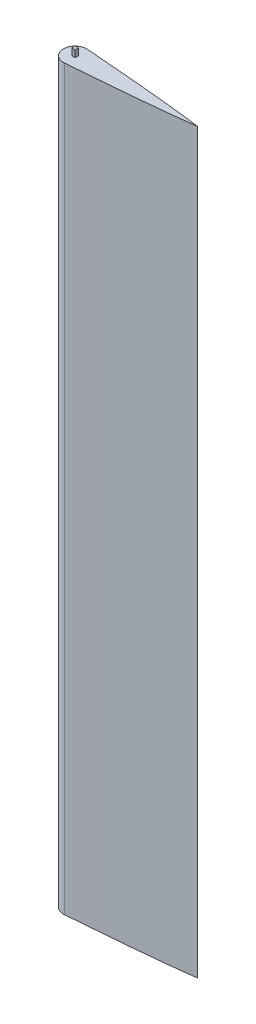
SolidWorks part; units mm, degrees
ref_plane "Front Plane" through (0, 0, 0) normal (0, 0, 1) x (1, 0, 0)
ref_plane "Top Plane" through (0, 0, 0) normal (0, 1, 0) x (1, 0, 0)
ref_plane "Right Plane" through (0, 0, 0) normal (1, 0, 0) x (0, 0, -1)
curve "Кривая1"
  spline degree 3 poles (1000, 0, 0) (1000.0041, 0, -0.0513) (1000.0182, 0, -0.2257) (1000.1688, 0, -0.5403) (1000.4745, 0, -0.9506) (1001.0036, 0, -1.4445) (1001.8807, 0, -2.0291) (1003.2737, 0, -2.6418) (1005.1875, 0, -3.2144) (1007.4906, 0, -3.7219) (1009.9978, 0, -4.1606) (1012.5898, 0, -4.5274) (1015.2222, 0, -4.8264) (1017.8799, 0, -5.0656) (1020.5573, 0, -5.2577) (1023.2491, 0, -5.4066) (1025.9511, 0, -5.5212) (1028.6617, 0, -5.6021) (1031.3775, 0, -5.6554) (1034.0978, 0, -5.6836) (1036.8218, 0, -5.6855) (1039.5499, 0, -5.6668) (1042.2813, 0, -5.629) (1045.0148, 0, -5.5734) (1047.7503, 0, -5.5016) (1050.4877, 0, -5.4147) (1053.2265, 0, -5.3143) (1055.9663, 0, -5.2015) (1058.7068, 0, -5.0768) (1061.4478, 0, -4.941) (1064.1895, 0, -4.7947) (1066.9318, 0, -4.6386) (1069.6745, 0, -4.4734) (1072.4174, 0, -4.2996) (1075.1604, 0, -4.1176) (1077.9035, 0, -3.9277) (1080.6469, 0, -3.7302) (1083.3903, 0, -3.5256) (1086.1334, 0, -3.3144) (1088.876, 0, -3.0964) (1091.618, 0, -2.8714) (1094.3597, 0, -2.6396) (1097.1011, 0, -2.4012) (1099.8418, 0, -2.1563) (1102.5808, 0, -1.9046) (1105.3171, 0, -1.6455) (1108.0495, 0, -1.3772) (1110.7765, 0, -1.0976) (1113.4879, 0, -0.8078) (1116.1278, 0, -0.5051) (1118.2949, 0, -0.236) (1119.5657, 0, -0.0601) (1120, 0, 0) knots 0 0 0 0 0.001266 0.004299 0.008398 0.013889 0.022051 0.034303 0.051281 0.071284 0.092472 0.114086 0.135878 0.157846 0.179936 0.202121 0.224378 0.246676 0.269043 0.291412 0.313814 0.336267 0.358739 0.381229 0.40374 0.426271 0.448818 0.471377 0.493944 0.51652 0.539106 0.561702 0.584306 0.606915 0.629529 0.652149 0.674775 0.697407 0.720041 0.742673 0.765305 0.787939 0.810576 0.833214 0.855845 0.878458 0.901044 0.923602 0.94611 0.968341 0.989179 1 1 1 1
curve "Кривая2"
  spline degree 3 poles (1120, 0, 0) (1119.5657, 0, 0.0601) (1118.2949, 0, 0.236) (1116.1278, 0, 0.5051) (1113.4879, 0, 0.8078) (1110.7765, 0, 1.0976) (1108.0495, 0, 1.3772) (1105.3171, 0, 1.6455) (1102.5808, 0, 1.9046) (1099.8418, 0, 2.1563) (1097.1011, 0, 2.4012) (1094.3597, 0, 2.6396) (1091.618, 0, 2.8714) (1088.876, 0, 3.0964) (1086.1334, 0, 3.3144) (1083.3903, 0, 3.5256) (1080.6469, 0, 3.7302) (1077.9035, 0, 3.9277) (1075.1604, 0, 4.1176) (1072.4174, 0, 4.2996) (1069.6745, 0, 4.4734) (1066.9318, 0, 4.6386) (1064.1895, 0, 4.7947) (1061.4478, 0, 4.941) (1058.7068, 0, 5.0768) (1055.9663, 0, 5.2015) (1053.2265, 0, 5.3143) (1050.4877, 0, 5.4147) (1047.7503, 0, 5.5016) (1045.0148, 0, 5.5734) (1042.2813, 0, 5.629) (1039.5499, 0, 5.6668) (1036.8218, 0, 5.6855) (1034.0978, 0, 5.6836) (1031.3775, 0, 5.6554) (1028.6617, 0, 5.6021) (1025.9511, 0, 5.5212) (1023.2491, 0, 5.4066) (1020.5573, 0, 5.2577) (1017.8799, 0, 5.0656) (1015.2222, 0, 4.8264) (1012.5898, 0, 4.5274) (1009.9978, 0, 4.1606) (1007.4906, 0, 3.7219) (1005.1875, 0, 3.2144) (1003.2737, 0, 2.6418) (1001.8807, 0, 2.0291) (1001.0036, 0, 1.4445) (1000.4745, 0, 0.9506) (1000.1688, 0, 0.5403) (1000.0182, 0, 0.2257) (1000.0041, 0, 0.0513) (1000, 0, 0) knots 0 0 0 0 0.010821 0.031659 0.05389 0.076398 0.098956 0.121542 0.144155 0.166786 0.189424 0.212061 0.234695 0.257327 0.279959 0.302593 0.325225 0.347851 0.370471 0.393085 0.415694 0.438298 0.460894 0.48348 0.506056 0.528623 0.551182 0.573729 0.59626 0.618771 0.641261 0.663733 0.686186 0.708588 0.730957 0.753324 0.775622 0.797879 0.820064 0.842154 0.864122 0.885914 0.907528 0.928716 0.948719 0.965697 0.977949 0.986111 0.991602 0.995701 0.998734 1 1 1 1
sketch "Эскиз2" plane through (0, 0, 0) normal (0, 1, 0) x (1, 0, 0)
  line L0 (1000, 0) -> (1120, 0) construction
  line L1 (1080, 14.3701) -> (1080, -24.9221) construction
  line L3 (1083.0057, -0.5) -> (1084.0057, -0.5)
  line L4 (1083.0057, -0.5) -> (1083.0057, 0.5)
  line L5 (1083.0057, 0.5) -> (1084.0057, 0.5)
  line L6 (1084.0057, -0.5) -> (1084.0057, 0.5)
  line L7 (1083.0057, -0.5) -> (1084.0057, 0.5) construction
  line L8 (1083.0057, 0.5) -> (1084.0057, -0.5) construction
  arc A0 (1083.7717, 3.4955) -> (1083.7717, -3.4955) centre (1083.5057, 0) ccw
  spline S0 degree 3 poles (1956.2165, -4926.245) (1230.5192, 53.0849) (1176.3623, 6.9741) (1116.1278, -0.5051) (1113.4879, -0.8078) (1110.7765, -1.0976) (1108.0495, -1.3772) (1105.3171, -1.6455) (1102.5808, -1.9046) (1099.8418, -2.1563) (1097.1011, -2.4012) (1094.3597, -2.6396) (1091.618, -2.8714) (1087.9619, -3.1714) (1083.3908, -3.5289) (1078.8184, -3.8643) (1074.2464, -4.1809) (1070.5892, -4.4183) (1066.9318, -4.6386) (1064.1895, -4.7947) (1060.5347, -4.9897) (1056.8803, -5.1639) (1053.2265, -5.3143) (1050.4877, -5.4147) (1046.8394, -5.5305) (1043.1934, -5.6163) (1039.5499, -5.6668) (1036.8218, -5.6855) (1034.0978, -5.6836) (1031.3775, -5.6554) (1028.6617, -5.6021) (1025.9511, -5.5212) (1023.2491, -5.4066) (1020.5573, -5.2577) (1017.8799, -5.0656) (1015.2222, -4.8264) (1012.5898, -4.5274) (1009.9978, -4.1606) (1007.4906, -3.7219) (1005.1875, -3.2144) (1003.2737, -2.6418) (1001.8807, -2.0291) (1001.0036, -1.4445) (1000.4745, -0.9506) (1000.1688, -0.5403) (997.8298, 4.3449) (1049.9935, 20.5033) (-3894.0582, -1012.3547) knots -1.443989 -1.443989 -1.443989 -1.443989 0.010821 0.031659 0.05389 0.076398 0.098956 0.121542 0.144155 0.166786 0.189424 0.212061 0.234695 0.257327 0.302593 0.347851 0.370471 0.415694 0.438298 0.460894 0.48348 0.528623 0.551182 0.573729 0.59626 0.641261 0.663733 0.686186 0.708588 0.730957 0.753324 0.775622 0.797879 0.820064 0.842154 0.864122 0.885914 0.907528 0.928716 0.948719 0.965697 0.977949 0.986111 0.991602 0.995701 0.998734 1.121986 1.121986 1.121986 1.121986 only from (1120, 0) to (1000, 0) construction
  spline S1 degree 3 poles (-3893.3459, 1012.2059) (1049.9886, -20.5018) (997.8299, -4.3447) (1000.1688, 0.5403) (1000.4745, 0.9506) (1001.0036, 1.4445) (1001.8807, 2.0291) (1003.2737, 2.6418) (1005.1875, 3.2144) (1007.4906, 3.7219) (1009.9978, 4.1606) (1012.5898, 4.5274) (1015.2222, 4.8264) (1017.8799, 5.0656) (1020.5573, 5.2577) (1023.2491, 5.4066) (1025.9511, 5.5212) (1028.6617, 5.6021) (1031.3775, 5.6554) (1034.0978, 5.6836) (1036.8218, 5.6855) (1039.5499, 5.6668) (1043.1934, 5.6163) (1046.8394, 5.5305) (1050.4877, 5.4147) (1053.2265, 5.3143) (1056.8803, 5.1639) (1060.5347, 4.9897) (1064.1895, 4.7947) (1066.9318, 4.6386) (1070.5892, 4.4183) (1074.2464, 4.1809) (1078.8184, 3.8643) (1082.4762, 3.596) (1086.1334, 3.3144) (1088.876, 3.0964) (1091.618, 2.8714) (1094.3597, 2.6396) (1097.1011, 2.4012) (1099.8418, 2.1563) (1102.5808, 1.9046) (1105.3171, 1.6455) (1108.0495, 1.3772) (1110.7765, 1.0976) (1113.4879, 0.8078) (1116.1278, 0.5051) (1176.3634, -6.9742) (1230.5211, -53.0865) (1956.254, 4926.5023) knots -0.12198 -0.12198 -0.12198 -0.12198 0.001266 0.004299 0.008398 0.013889 0.022051 0.034303 0.051281 0.071284 0.092472 0.114086 0.135878 0.157846 0.179936 0.202121 0.224378 0.246676 0.269043 0.291412 0.313814 0.336267 0.358739 0.40374 0.426271 0.448818 0.471377 0.51652 0.539106 0.561702 0.584306 0.629529 0.652149 0.697407 0.720041 0.742673 0.765305 0.787939 0.810576 0.833214 0.855845 0.878458 0.901044 0.923602 0.94611 0.968341 0.989179 2.444014 2.444014 2.444014 2.444014 only from (1000, 0) to (1120, 0) construction
  spline S2 degree 3 poles (1120, 0) (1119.5657, -0.0601) (1118.2949, -0.236) (1116.1278, -0.5051) (1113.4879, -0.8078) (1110.7765, -1.0976) (1108.0495, -1.3772) (1105.3171, -1.6455) (1102.5808, -1.9046) (1099.8418, -2.1563) (1097.1011, -2.4012) (1094.3597, -2.6396) (1091.618, -2.8714) (1087.9619, -3.1714) (1083.3908, -3.5289) (1078.8184, -3.8643) (1074.2464, -4.1809) (1070.5892, -4.4183) (1066.9318, -4.6386) (1064.1895, -4.7947) (1060.5347, -4.9897) (1056.8803, -5.1639) (1053.2265, -5.3143) (1050.4877, -5.4147) (1046.8394, -5.5305) (1043.1934, -5.6163) (1039.5499, -5.6668) (1036.8218, -5.6855) (1034.0978, -5.6836) (1031.3775, -5.6554) (1028.6617, -5.6021) (1025.9511, -5.5212) (1023.2491, -5.4066) (1020.5573, -5.2577) (1017.8799, -5.0656) (1015.2222, -4.8264) (1012.5898, -4.5274) (1009.9978, -4.1606) (1007.4906, -3.7219) (1005.1875, -3.2144) (1003.2737, -2.6418) (1001.8807, -2.0291) (1001.0036, -1.4445) (1000.4745, -0.9506) (1000.1688, -0.5403) (1000.0182, -0.2257) (1000.0041, -0.0513) (1000, 0) knots 0 0 0 0 0.010821 0.031659 0.05389 0.076398 0.098956 0.121542 0.144155 0.166786 0.189424 0.212061 0.234695 0.257327 0.302593 0.347851 0.370471 0.415694 0.438298 0.460894 0.48348 0.528623 0.551182 0.573729 0.59626 0.641261 0.663733 0.686186 0.708588 0.730957 0.753324 0.775622 0.797879 0.820064 0.842154 0.864122 0.885914 0.907528 0.928716 0.948719 0.965697 0.977949 0.986111 0.991602 0.995701 0.998734 1 1 1 1
  spline S3 degree 3 poles (1000, 0) (1000.0041, 0.0513) (1000.0182, 0.2257) (1000.1688, 0.5403) (1000.4745, 0.9506) (1001.0036, 1.4445) (1001.8807, 2.0291) (1003.2737, 2.6418) (1005.1875, 3.2144) (1007.4906, 3.7219) (1009.9978, 4.1606) (1012.5898, 4.5274) (1015.2222, 4.8264) (1017.8799, 5.0656) (1020.5573, 5.2577) (1023.2491, 5.4066) (1025.9511, 5.5212) (1028.6617, 5.6021) (1031.3775, 5.6554) (1034.0978, 5.6836) (1036.8218, 5.6855) (1039.5499, 5.6668) (1043.1934, 5.6163) (1046.8394, 5.5305) (1050.4877, 5.4147) (1053.2265, 5.3143) (1056.8803, 5.1639) (1060.5347, 4.9897) (1064.1895, 4.7947) (1066.9318, 4.6386) (1070.5892, 4.4183) (1074.2464, 4.1809) (1078.8184, 3.8643) (1082.4762, 3.596) (1086.1334, 3.3144) (1088.876, 3.0964) (1091.618, 2.8714) (1094.3597, 2.6396) (1097.1011, 2.4012) (1099.8418, 2.1563) (1102.5808, 1.9046) (1105.3171, 1.6455) (1108.0495, 1.3772) (1110.7765, 1.0976) (1113.4879, 0.8078) (1116.1278, 0.5051) (1118.2949, 0.236) (1119.5657, 0.0601) (1120, 0) knots 0 0 0 0 0.001266 0.004299 0.008398 0.013889 0.022051 0.034303 0.051281 0.071284 0.092472 0.114086 0.135878 0.157846 0.179936 0.202121 0.224378 0.246676 0.269043 0.291412 0.313814 0.336267 0.358739 0.40374 0.426271 0.448818 0.471377 0.51652 0.539106 0.561702 0.584306 0.629529 0.652149 0.697407 0.720041 0.742673 0.765305 0.787939 0.810576 0.833214 0.855845 0.878458 0.901044 0.923602 0.94611 0.968341 0.989179 1 1 1 1
  dimension "D2" = 1
  dimension "D1" = 40
extrude "Бобышка-Вытянуть1" add sketch "Эскиз2" along normal blind 220 contours S3 A0 S2 region at (1094.6152, 0, 0)
extrude "Бобышка-Вытянуть2" add sketch "Эскиз2<3>" along normal blind 224 from offset 2 contours L3 L6 L5 L4 region at (1083.5057, 0, 0) offset against normal yes
sketch "Эскиз2<3>" plane through (0, 0, 0) normal (0, 1, 0) x (1, 0, 0) same geometry as "Эскиз2"
